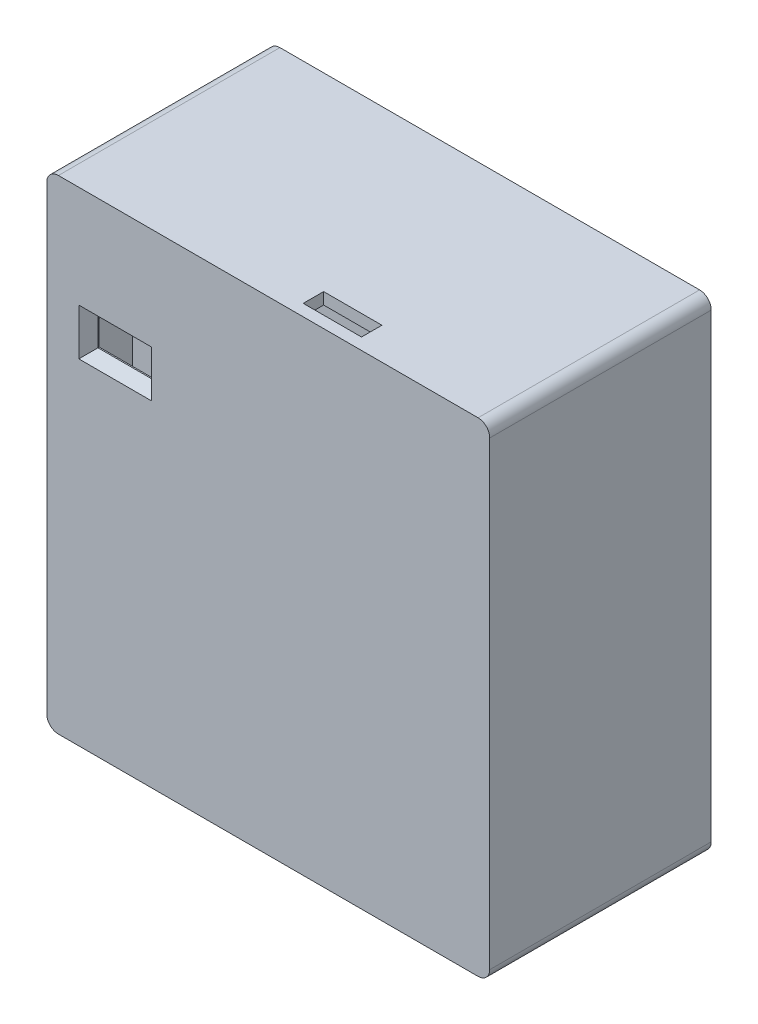
SolidWorks part; units mm, degrees
ref_plane "Front Plane" through (0, 0, 0) normal (0, 0, 1) x (1, 0, 0)
ref_plane "Top Plane" through (0, 0, 0) normal (0, 1, 0) x (1, 0, 0)
ref_plane "Right Plane" through (0, 0, 0) normal (1, 0, 0) x (0, 0, -1)
sketch "Sketch1" plane through (0, 0, 0) normal (0, 1, 0) x (1, 0, 0)
  line L0 (-38, 19) -> (38, 19)
  line L1 (-36, -17) -> (36, -17)
  line L2 (-36, -17) -> (-36, 17)
  line L3 (-36, 17) -> (36, 17)
  line L4 (36, -17) -> (36, 17)
  line L5 (-36, -17) -> (36, 17) construction
  line L6 (-36, 17) -> (36, -17) construction
  line L7 (38, -19) -> (38, 19)
  line L8 (-38, -19) -> (38, -19)
  line L9 (-38, -19) -> (-38, 19)
  point P0 (0, 0)
  dimension "D1" = 34
  dimension "D2" = 72
  dimension "D3" = 2
extrude "Boss-Extrude2" add sketch "Sketch1" along normal blind 39.5 and the other way blind 39.5
sketch "Sketch2" plane through (0, -39.5, 0) normal (0, -1, 0) x (1, 0, 0)
  line L1 (-38, -19) -> (38, -19)
  line L2 (-38, -19) -> (-38, 19)
  line L3 (-38, 19) -> (38, 19)
  line L4 (38, -19) -> (38, 19)
  line L5 (-38, -19) -> (38, 19) construction
  line L6 (-38, 19) -> (38, -19) construction
  point P0 (0, 0)
extrude "Boss-Extrude3" add sketch "Sketch2" along normal blind 2
mirror "Mirror1" about plane through (0, 0, 0) normal (0, 1, 0) of "Boss-Extrude3"
sketch "Sketch6" plane through (0, 0, 0) normal (0, 0, 1) x (1, 0, 0)
  line L1 (-35, -31.5) -> (35, -31.5)
  line L2 (-35, -31.5) -> (-35, 38.5)
  line L3 (-35, 38.5) -> (35, 38.5)
  line L4 (35, -31.5) -> (35, 38.5)
  line L5 (-35, -31.5) -> (35, 38.5) construction
  line L6 (-35, 38.5) -> (35, -31.5) construction
  line L7 (36, 39.5) -> (-36, 39.5) construction
  point P0 (0, 3.5)
  dimension "D1" = 70
  dimension "D2" = 70
  dimension "D3" = 1
extrude "Boss-Extrude4" add sketch "Sketch6" along normal blind 10 and the other way blind 10
fillet "Fillet1" radius 2 4 edges at (-38, 41.5, 0) (-38, -41.5, 0) (38, -41.5, 0) (38, 41.5, 0)
ref_plane "Plane1" through (0, 0, 16) normal (0, 0, 1) x (1, 0, 0)
sketch "Sketch7" plane through (0, 0, 16) normal (0, 0, 1) x (1, 0, 0)
  line L1 (-38, -20.6) -> (-36, -20.6)
  line L2 (-38, -20.6) -> (-38, -10.6)
  line L3 (-38, -10.6) -> (-36, -10.6)
  line L4 (-36, -20.6) -> (-36, -10.6)
  line L5 (-36, -39.5) -> (-36, 39.5) construction
  line L6 (-36, 41.5) -> (36, 41.5) construction
  line L7 (4, 41.5) -> (14, 41.5)
  line L8 (4, 41.5) -> (4, 39.5)
  line L9 (4, 39.5) -> (14, 39.5)
  line L10 (14, 41.5) -> (14, 39.5)
  line L11 (36, 39.5) -> (-36, 39.5) construction
  line L12 (-35, 38.5) -> (-35, -31.5) construction
  dimension "D1" = 10
  dimension "D2" = 10
  dimension "D3" = 39
  dimension "D4" = 10.6
  dimension "D5" = 2
extrude "Cut-Extrude1" cut sketch "Sketch7" against normal blind 2.5 and the other way blind 1
sketch "Sketch8" plane through (-38, 0, 0) normal (-1, 0, 0) x (0, 0, 1)
  line L0 (-19, -39.5) -> (-19, 39.5) construction
  circle A0 centre (-6.625, 8) radius 6.5
  dimension "D1" = 13
  dimension "D2" = 12.375
  dimension "D3" = 8
extrude "Cut-Extrude2" cut sketch "Sketch8" against normal up to next (2 mm away)
sketch "Sketch9" plane through (0, 0, -17) normal (0, 0, 1) x (1, 0, 0)
  line L0 (-36, -39.5) -> (-36, 39.5) construction
  line L1 (-22.5, 17.75) -> (-2.5, 17.75)
  line L2 (-22.5, 17.75) -> (-22.5, 24.75)
  line L3 (-22.5, 24.75) -> (-2.5, 24.75)
  line L4 (-2.5, 17.75) -> (-2.5, 24.75)
  line L5 (-22.5, -29.75) -> (2.5, -29.75)
  line L6 (-22.5, -29.75) -> (-22.5, -22.75)
  line L7 (-22.5, -22.75) -> (2.5, -22.75)
  line L8 (2.5, -29.75) -> (2.5, -22.75)
  line L9 (-2.5, 17.75) -> (-2.5, -22.75) construction
  line L10 (12, 7.5) -> (5, 7.5)
  line L11 (12, 7.5) -> (12, -12.5)
  line L12 (12, -12.5) -> (5, -12.5)
  line L13 (5, 7.5) -> (5, -12.5)
  point P10 (5, -2.5)
  point P12 (-2.5, -2.5)
  dimension "D1" = 40.5
  dimension "D2" = 7
  dimension "D3" = 7
  dimension "D4" = 20
  dimension "D5" = 25
  dimension "D6" = 17.75
  dimension "D7" = 7
  dimension "D8" = 20
  dimension "D9" = 27.5
  dimension "D10" = 41
extrude "Boss-Extrude5" add sketch "Sketch9" along normal blind 10
sketch "Sketch10" plane through (0, 0, 19) normal (0, 0, 1) x (1, 0, 0)
  line L0 (36, 41.5) -> (-36, 41.5) construction
  line L1 (-21.5, 22.5) -> (-31, 22.5)
  line L2 (-21.5, 22.5) -> (-21.5, 17.5)
  line L3 (-21.5, 17.5) -> (-31, 17.5)
  line L4 (-31, 22.5) -> (-31, 17.5)
  line L5 (-38, -39.5) -> (-38, 39.5) construction
  dimension "D1" = 5
  dimension "D2" = 9.5
  dimension "D3" = 19
  dimension "D4" = 7
extrude "Cut-Extrude3" cut sketch "Sketch10" against normal up to next (2 mm away)
chamfer "Chamfer1" distance 1.5 angle 50 4 edges at (-31, 20, 19) (-26.25, 22.5, 19) (-26.25, 17.5, 19) (-21.5, 20, 19) first distance on face at (-26.25, 20, 19)
sketch "Sketch11" plane through (0, 0, 17) normal (0, 0, -1) x (-1, 0, 0)
  line L0 (36, -10.6) -> (36, 39.5) construction
  line L3 (36, 20.5) -> (32.3, 20.5)
  line L4 (36, 20.5) -> (36, 4.5)
  line L5 (36, 4.5) -> (32.3, 4.5)
  line L6 (32.3, 20.5) -> (32.3, 4.5)
  line L8 (36, 39.5) -> (-4, 39.5) construction
  line L9 (21.5, 17.5) -> (31, 17.5) construction
  line L10 (-36, -39.5) -> (-36, 39.5) construction
  line L11 (-36, 20) -> (-29, 20)
  line L12 (-36, 20) -> (-36, 15)
  line L13 (-36, 15) -> (-29, 15)
  line L14 (-29, 20) -> (-29, 15)
  line L16 (-36, -26.5) -> (-29, -26.5)
  line L17 (-36, -26.5) -> (-36, -31.5)
  line L18 (-36, -31.5) -> (-29, -31.5)
  line L19 (-29, -26.5) -> (-29, -31.5)
  circle A3 centre (33.85, 17.5) radius 1.25
  circle A4 centre (-32.15, 17.5) radius 1.25
  circle A5 centre (-32.15, -29) radius 1.25
  dimension "D1" = 3.7
  dimension "D2" = 16
  dimension "D3" = 13
  dimension "D4" = 2.5
  dimension "D8" = 2.5
  dimension "D9" = 2.5
  dimension "D5" = 2.15
  dimension "D6" = 22
  dimension "D7" = 66
  dimension "D10" = 46.5
  dimension "D11" = 7
  dimension "D12" = 5
  dimension "D13" = 2.5
  dimension "D14" = 5
  dimension "D15" = 7
  dimension "D16" = 2.5
extrude "Boss-Extrude10" add sketch "Sketch11" along normal blind 7.3
sketch "Sketch13" plane through (36, 0, 0) normal (-1, 0, 0) x (0, 0, 1)
  line L0 (9.7, -26.5) -> (17, -26.5) construction
  circle A0 centre (0, -21.5) radius 2
  dimension "D1" = 4
  dimension "D2" = 5
extrude "Cut-Extrude4" [suppressed] cut sketch "Sketch13" against normal through all
sketch "Sketch15" plane through (0, 0, 0) normal (0, 0, 1) x (1, 0, 0)
  line L0 (29, -31.5) -> (29, -26.5) construction
  line L2 (29, -26.5) -> (36, -26.5) construction
  line L3 (28, -20) -> (28, -25) construction
  line L4 (30.5, -22.5) -> (25.5, -22.5) construction
  line L5 (30.4875, -22.25) -> (25.5125, -22.25)
  line L6 (27.75, -24.9875) -> (27.75, -20.0125)
  line L7 (28.25, -24.9875) -> (28.25, -20.0125)
  line L8 (30.4875, -22.75) -> (25.5125, -22.75)
  circle A0 centre (28, -22.5) radius 2.5
  dimension "D1" = 5
  dimension "D2" = 1
  dimension "D3" = 4
  dimension "D4" = 0.25
  dimension "D5" = 0.25
extrude "Cut-Extrude6" cut sketch "Sketch15" against normal through all contours L5 A0 L7 | L6 A0 L5 | L8 A0 L6 | L7 A0 L8 region at (29.1709, -21.3291, 0) region at (26.8291, -21.3291, 0) region at (29.1709, -23.6709, 0) region at (26.8291, -23.6709, 0)
sketch "Sketch16" plane through (0, 0, 17) normal (0, 0, -1) x (-1, 0, 0)
  line L0 (-14, 39.5) -> (-36, 39.5) construction
  line L1 (-36, 20) -> (-36, 39.5) construction
  line L2 (-36, 32.6841) -> (-29.1841, 39.5)
  line L3 (29.1841, -39.5) -> (36, -32.6841)
  line L4 (36, -39.5) -> (-36, -39.5) construction
  line L5 (36, -39.5) -> (36, -20.6) construction
  line L6 (-36, 32.6841) -> (-36, 39.5)
  line L7 (-36, 39.5) -> (-29.1841, 39.5)
  line L8 (29.1841, -39.5) -> (36, -39.5)
  line L9 (36, -39.5) -> (36, -32.6841)
  circle A0 centre (-34.625, 38.125) radius 1.375
  circle A2 centre (34.625, -38.125) radius 1.375
  circle A4 centre (-34.625, 38.125) radius 2.875
  circle A5 centre (34.625, -38.125) radius 2.875
  line M8 (-36, -39.5) -> (36, -39.5)
  line M9 (36, -39.5) -> (36, -20.6)
  line M22 (-14, 39.5) -> (-36, 39.5)
  line M23 (-36, 39.5) -> (-36, 20)
  dimension "D1" = 2.75
  dimension "D3" = 5.75
  dimension "D7" = 2.75
  dimension "D4" = 5.75
  dimension "D2" = 45
  dimension "D6" = 45
extrude "Boss-Extrude11" add sketch "Sketch16" along normal through all contours A4 L2 M23 | L6 A4 L7 A0 | A4 L2 M22 | A0 L7 M23 | A2 L8 M9 | L9 A5 L8 A2 | A5 L3 M9 | A5 L3 M8 region at (35.0866, 34.4865, 17) region at (30.9865, 38.5866, 17) region at (33.6128, 37.1128, 17) region at (35.6929, 39.1929, 17) region at (-30.9865, -38.5866, 17) region at (-35.0866, -34.4865, 17) region at (-33.6128, -37.1128, 17) region at (-35.6929, -39.1929, 17)
sketch "Sketch17" plane through (0, 0, -19) normal (0, 0, -1) x (-1, 0, 0)
  circle A0 centre (-34.625, 38.125) radius 2.75
  circle A1 centre (34.625, -38.125) radius 2.75
  circle A2 centre (-34.625, 38.125) radius 1.375 construction
  circle A3 centre (34.625, -38.125) radius 1.375 construction
  dimension "D1" = 5.5
  dimension "D2" = 5.5
extrude "Cut-Extrude9" cut sketch "Sketch17" against normal blind 3
ref_plane "Plane2" [suppressed] through (0, 0, -5.8) normal (0, 0, 1) x (1, 0, 0)
sketch "Sketch14" [suppressed] plane through (0, 0, -5.8) normal (0, 0, 1) x (1, 0, 0)
  line L1 (-39.0134, 43.131) -> (40.5107, 43.131)
  line L2 (-39.0134, 43.131) -> (-39.0134, -43.0478)
  line L3 (-39.0134, -43.0478) -> (40.5107, -43.0478)
  line L4 (40.5107, 43.131) -> (40.5107, -43.0478)
extrude "Cut-Extrude7" [suppressed] cut sketch "Sketch14" against normal through all
